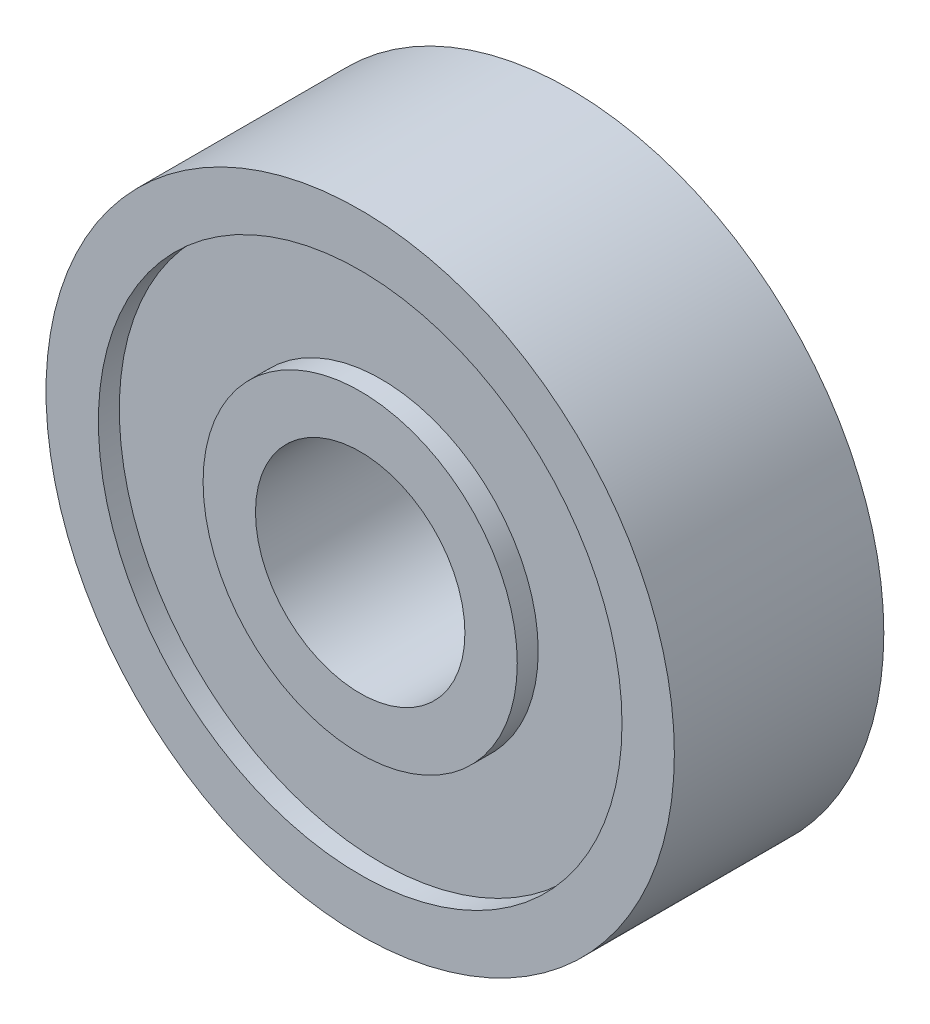
SolidWorks part; units mm, degrees
ref_plane "Front Plane" through (0, 0, 0) normal (0, 0, 1) x (1, 0, 0)
ref_plane "Top Plane" through (0, 0, 0) normal (0, 1, 0) x (1, 0, 0)
ref_plane "Right Plane" through (0, 0, 0) normal (1, 0, 0) x (0, 0, -1)
sketch "Sketch2" plane through (0, 0, 0) normal (0, 0, 1) x (1, 0, 0)
  circle A0 centre (0, 0) radius 12.5
  circle A1 centre (0, 0) radius 5
  circle A2 centre (0, 0) radius 7.5
  circle A3 centre (0, 0) radius 15
  dimension "D1" = 10
  dimension "D2" = 30
  dimension "D3" = 15
  dimension "D4" = 25
extrude "Boss-Extrude1" add sketch "Sketch2" along normal blind 10 contours A3 A0 | A2 A1 region at (-7.2879, 0, 0) region at (-14.5757, 0, 0)
extrude "Boss-Extrude2" add sketch "Sketch2<3>" along normal blind 9 contours A0 A2 region at (-12.1464, 0, 0)
sketch "Sketch2<3>" plane through (0, 0, 0) normal (0, 0, 1) x (1, 0, 0) same geometry as "Sketch2"
